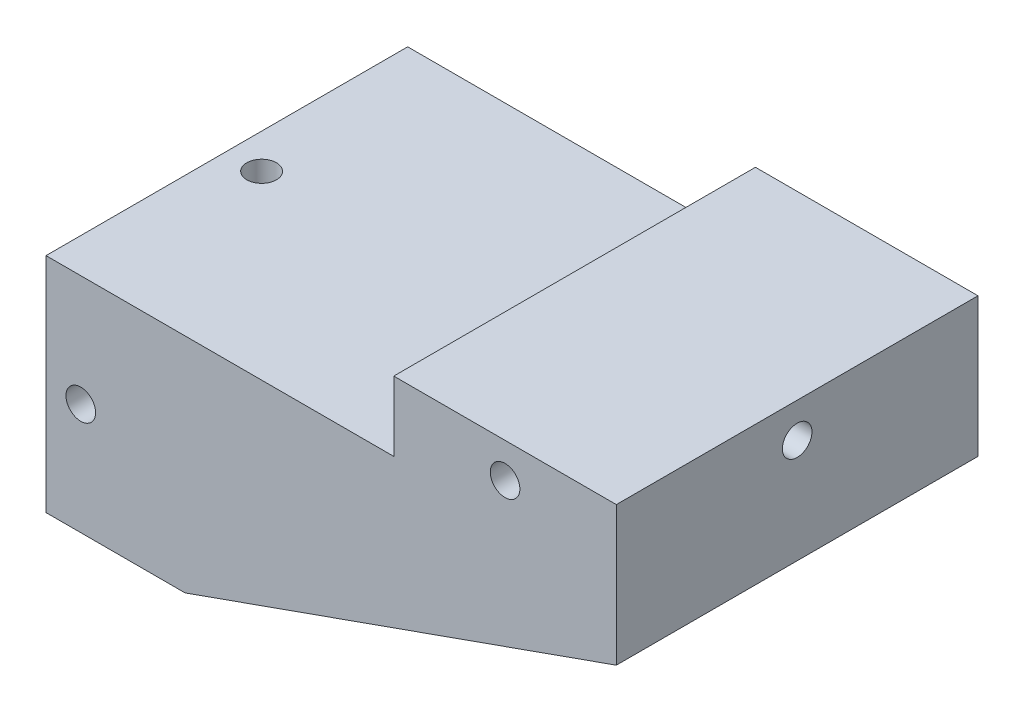
SolidWorks part; units mm, degrees
ref_plane "Front Plane" through (0, 0, 0) normal (0, 0, 1) x (1, 0, 0)
ref_plane "Top Plane" through (0, 0, 0) normal (0, 1, 0) x (1, 0, 0)
ref_plane "Right Plane" through (0, 0, 0) normal (1, 0, 0) x (0, 0, -1)
sketch "Sketch1" plane through (0, 0, 0) normal (1, 0, 0) x (0, 0, -1)
  line L1 (-16.51, -10.16) -> (16.51, -10.16)
  line L2 (-16.51, -10.16) -> (-16.51, 10.16)
  line L3 (-16.51, 10.16) -> (16.51, 10.16)
  line L4 (16.51, -10.16) -> (16.51, 10.16)
  line L5 (-16.51, -10.16) -> (16.51, 10.16) construction
  line L6 (-16.51, 10.16) -> (16.51, -10.16) construction
  point P0 (0, 0)
  dimension "D1" = 33.02
  dimension "D2" = 20.32
extrude "Boss-Extrude1" add sketch "Sketch1" along normal blind 6.35
sketch "Sketch2" plane through (0, 10.16, 0) normal (0, 1, 0) x (1, 0, 0)
  line L1 (52.07, -16.51) -> (31.75, -16.51)
  line L2 (52.07, -16.51) -> (52.07, 16.51)
  line L3 (52.07, 16.51) -> (31.75, 16.51)
  line L4 (31.75, -16.51) -> (31.75, 16.51)
  line L6 (6.35, -16.51) -> (0, -16.51) construction
  line L7 (6.35, 16.51) -> (6.35, -16.51) construction
  dimension "D1" = 33.02
  dimension "D2" = 20.32
  dimension "D3" = 25.4
extrude "Boss-Extrude2" add sketch "Sketch2" along normal blind 6.35 separate body
hole_wizard "#6-32 Tapped Hole1" positions "3DSketch1" profile "Sketch5" tap size "#6-32" standard "ANSI Inch"
sketch3d "3DSketch1"
  line L0 (3.175, 10.16, -16.51) -> (3.175, -10.16, -16.51) construction
  line L1 (6.35, 10.16, -16.51) -> (0, 10.16, -16.51) construction
  line L2 (6.35, -10.16, -16.51) -> (0, -10.16, -16.51) construction
  line L8 (31.75, 13.335, -16.51) -> (52.07, 13.335, -16.51) construction
  line L9 (31.75, 16.51, -16.51) -> (31.75, 10.16, -16.51) construction
  line L10 (52.07, 10.16, -16.51) -> (52.07, 16.51, -16.51) construction
  line L13 (31.75, 13.335, -16.51) -> (31.75, 13.335, 16.51) construction
  line L14 (31.75, 16.51, 16.51) -> (31.75, 10.16, 16.51) construction
  line L16 (3.175, 10.16, -16.51) -> (3.175, 10.16, 16.51) construction
  line L17 (6.35, 10.16, 16.51) -> (0, 10.16, 16.51) construction
  line L18 (6.35, 10.16, 16.51) -> (0, 10.16, 16.51) construction
  line L19 (6.35, 10.16, -16.51) -> (0, 10.16, -16.51) construction
  point P40 (3.175, 0, -16.51)
  point P42 (3.175, 10.16, 0)
  point P44 (31.75, 13.335, 0)
  point P46 (41.91, 13.335, -16.51)
  point P57 (41.91, 13.335, 16.51)
  point P59 (52.07, 13.335, 0)
  point P61 (3.175, 0, 16.51)
  point P63 (3.175, -10.16, 0)
sketch "Sketch5" plane through (3.175, 0, -16.51) normal (1, 0, 0) x (0, 1, 0)
  line L0 (0, 0) -> (0, 9.4487)
  line L1 (0, 9.4487) -> (1.3525, 8.636)
  line L2 (1.3525, 8.636) -> (1.3525, 0)
  line L5 (1.3525, 0) -> (0, 0)
  line L10 (0, 9.4487) -> (-1.3526, 8.636) construction
  line L11 (0, -6.35) -> (0, 107.95) construction
  dimension "Tap Drill Dia." = 2.7051
  dimension "Tap Drill Depth" = 8.636
  dimension "Drill Angle" = 118
sketch "Sketch4" plane through (0, 0, -16.51) normal (0, 0, 1) x (1, 0, 0)
  line L0 (52.07, 10.16) -> (52.07, 3.81)
  line L1 (52.07, 3.81) -> (12.7, -10.16)
  line L2 (12.7, -10.16) -> (6.35, -10.16)
  line L3 (52.07, 10.16) -> (6.35, 10.16)
  line L4 (6.35, 10.16) -> (6.35, -10.16)
  dimension "D1" = 6.35
extrude "Boss-Extrude3" add sketch "Sketch4" along normal through all
